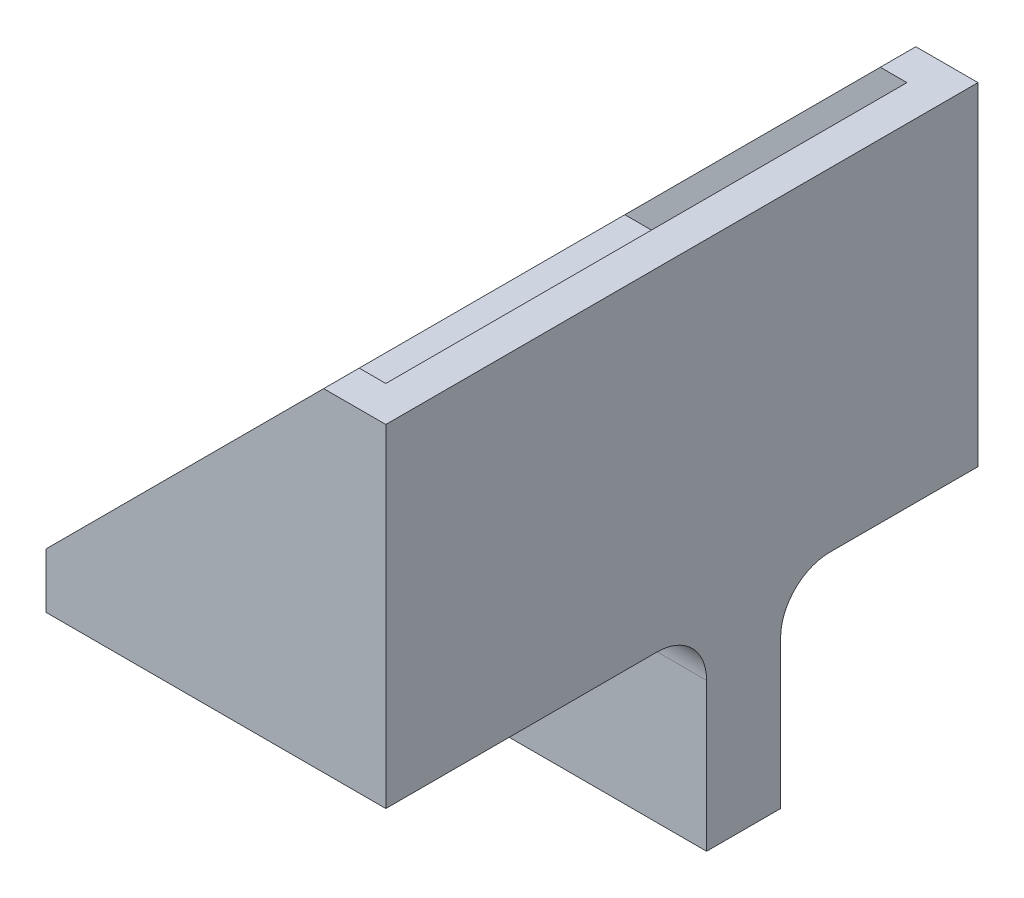
SolidWorks part; units mm, degrees
ref_plane "Front Plane" through (0, 0, 0) normal (0, 0, 1) x (1, 0, 0)
ref_plane "Top Plane" through (0, 0, 0) normal (0, 1, 0) x (1, 0, 0)
ref_plane "Right Plane" through (0, 0, 0) normal (1, 0, 0) x (0, 0, -1)
sketch "Sketch1" plane through (0, 0, 0) normal (0, 0, 1) x (1, 0, 0)
  line L0 (30.841, 29.7939) -> (-19.959, -21.0061)
  line L3 (-19.959, -21.0061) -> (30.841, -21.0061)
  line L4 (30.841, 29.7939) -> (30.841, -21.0061)
  dimension "D1" = 50.8
extrude "Boss-Extrude1" add sketch "Sketch1" along normal blind 76.2
sketch "Sketch2" plane through (0, 0, 0) normal (0, 1, 0) x (1, 0, 0)
  line L0 (-19.959, -76.2) -> (-19.959, 0) construction
  line L1 (-19.959, -4.572) -> (26.269, -4.572)
  line L2 (-19.959, -4.572) -> (-19.959, -71.628)
  line L3 (-19.959, -71.628) -> (26.269, -71.628)
  line L4 (26.269, -4.572) -> (26.269, -71.628)
  line L5 (30.841, 0) -> (-19.959, 0) construction
  line L6 (30.841, -76.2) -> (-19.959, -76.2) construction
  line L7 (30.841, -76.2) -> (30.841, 0) construction
  dimension "D1" = 4.572
  dimension "D2" = 4.572
  dimension "D3" = 4.572
extrude "Cut-Extrude1" cut sketch "Sketch2" along normal blind 32 and the other way blind 11.079
chamfer "Chamfer2" distance 8 angle 90 1 edges at (30.841, 29.7939, 38.1) first distance on face at (30.841, 4.3939, 38.1)
chamfer "Chamfer3" distance 10 angle 45 1 edges at (-19.959, -21.0061, 38.1) first distance on face at (3.9228, 2.8757, 38.1)
sketch "Sketch3" plane through (0, -11.079, 0) normal (0, 1, 0) x (1, 0, 0)
  line L2 (30.841, -25.4) -> (-12.8879, 0) construction
  line L3 (30.841, 0) -> (-12.8879, 0) construction
  line L4 (30.841, 0) -> (30.841, -25.4) construction
  line L5 (30.841, -25.4) -> (-12.8879, -25.4) construction
  line L6 (-12.8879, -76.2) -> (30.841, -76.2)
  line L7 (-12.8879, 0) -> (-12.8879, -76.2)
  line L8 (30.841, 0) -> (-12.8879, 0)
  line L9 (30.841, -76.2) -> (30.841, 0)
  line L10 (-12.8879, -76.2) -> (30.841, -76.2) construction
  line L11 (-12.8879, 0) -> (-12.8879, -76.2) construction
  line L12 (30.841, 0) -> (-12.8879, 0) construction
  line L13 (30.841, -76.2) -> (30.841, 0) construction
  line L14 (-12.8879, 0) -> (-12.8879, -25.4) construction
  circle A0 centre (8.9766, -12.7) radius 3.175
  dimension "D1" = 0
  dimension "D2" = 25.4
extrude "Cut-Extrude2" cut sketch "Sketch3" against normal through all contours A0
sketch "Sketch8" plane through (0, -21.0061, 0) normal (0, -1, 0) x (1, 0, 0)
  line L0 (30.841, 76.2) -> (30.841, 0) construction
  line L1 (-12.8879, 0) -> (30.841, 0) construction
  line L2 (-12.8879, 0) -> (-12.8879, 25.4) construction
  line L3 (-12.8879, 25.4) -> (30.841, 25.4) construction
  line L4 (30.841, 0) -> (30.841, 25.4) construction
  line L6 (-12.8879, 25.4) -> (30.841, 25.4)
  line L7 (-12.8879, 25.4) -> (-12.8879, 34.925)
  line L8 (-12.8879, 34.925) -> (30.841, 34.925)
  line L9 (30.841, 25.4) -> (30.841, 34.925)
  dimension "D1" = 25.4
  dimension "D2" = 9.525
extrude "Boss-Extrude3" add sketch "Sketch8" along normal blind 25.4
sketch "Sketch9" plane through (0, 0, 34.925) normal (0, 0, 1) x (1, 0, 0)
  circle A0 centre (8.9766, -33.7061) radius 3.175
extrude "Cut-Extrude3" cut sketch "Sketch9" against normal through all
fillet "Fillet2" radius 6.35 2 edges at (8.9766, -21.0061, 25.4) (8.9766, -21.0061, 34.925)
